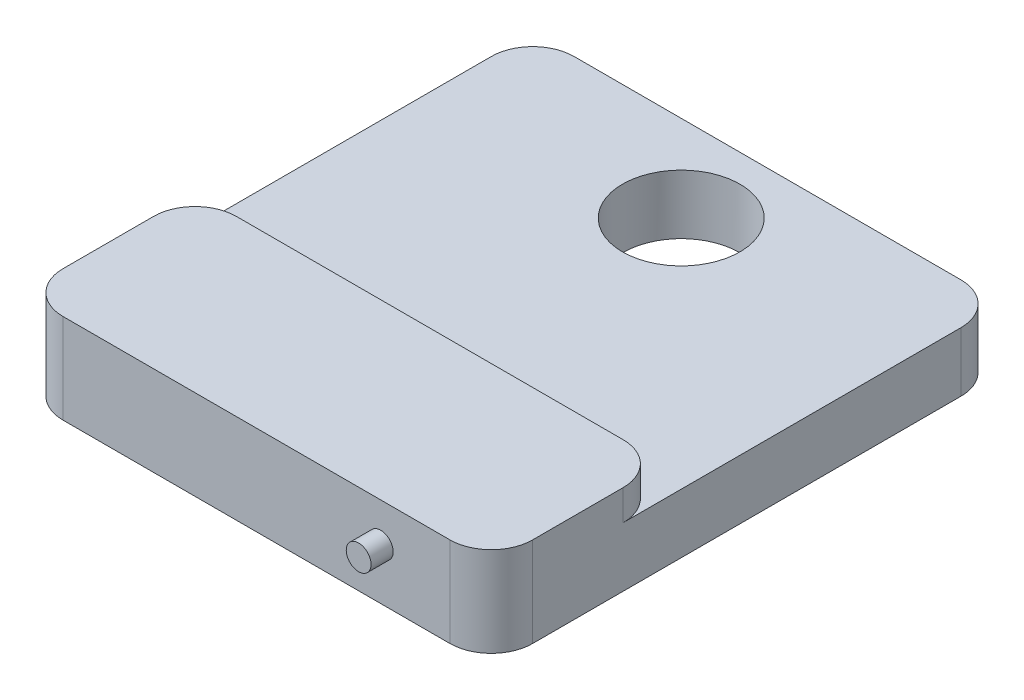
SolidWorks part; units mm, degrees
material "ABS"
ref_plane "Front Plane" through (0, 0, 0) normal (0, 0, 1) x (1, 0, 0)
ref_plane "Top Plane" through (0, 0, 0) normal (0, 1, 0) x (1, 0, 0)
ref_plane "Right Plane" through (0, 0, 0) normal (1, 0, 0) x (0, 0, -1)
sketch "Sketch1" plane through (0, 0, 0) normal (0, 1, 0) x (1, 0, 0)
  line L1 (0, 0) -> (215.9, 0)
  line L2 (0, 0) -> (0, 234.95)
  line L3 (0, 234.95) -> (215.9, 234.95)
  line L4 (215.9, 0) -> (215.9, 234.95)
  dimension "D1" = 234.95
  dimension "D2" = 215.9
extrude "Boss-Extrude1" add sketch "Sketch1" along normal blind 41.275
fillet "Fillet1" radius 19.05 4 edges at (0, 20.6375, -234.95) (215.9, 20.6375, -234.95) (215.9, 20.6375, 0) (0, 20.6375, 0)
sketch "Sketch3" plane through (0, 41.275, 0) normal (0, 1, 0) x (1, 0, 0)
  line L0 (107.95, 234.95) -> (107.95, 0) construction
  line L1 (196.85, 234.95) -> (19.05, 234.95) construction
  line L2 (19.05, 0) -> (196.85, 0) construction
  circle A0 centre (107.95, 195.2625) radius 26.9875
  point P8 (107.95, 222.25)
  dimension "D1" = 53.975
  dimension "D2" = 12.7
extrude "Cut-Extrude1" cut sketch "Sketch3" against normal up to next
sketch "Sketch4" plane through (0, 41.275, 0) normal (0, 1, 0) x (1, 0, 0)
  line L0 (215.9, 79.6925) -> (0, 79.6925)
  line L1 (215.9, 19.05) -> (215.9, 215.9) construction
  line L3 (196.85, 234.95) -> (19.05, 234.95) construction
  line L4 (0, 215.9) -> (0, 19.05) construction
  line L6 (196.85, 234.95) -> (19.05, 234.95)
  line L7 (215.9, 79.6925) -> (215.9, 215.9)
  line L8 (0, 215.9) -> (0, 79.6925)
  line L9 (19.05, 0) -> (196.85, 0) construction
  arc A0 (19.05, 234.95) -> (0, 215.9) centre (19.05, 215.9) ccw construction
  arc A1 (215.9, 215.9) -> (196.85, 234.95) centre (196.85, 215.9) ccw construction
  arc A4 (19.05, 234.95) -> (0, 215.9) centre (19.05, 215.9) ccw
  arc A5 (215.9, 215.9) -> (196.85, 234.95) centre (196.85, 215.9) ccw
  dimension "D1" = 79.6925
extrude "Cut-Extrude2" cut sketch "Sketch4" against normal blind 13.97
fillet "Fillet2" radius 19.05 2 edges at (0, 34.29, -79.6925) (215.9, 34.29, -79.6925)
sketch "Sketch5" plane through (0, 0, 0) normal (0, 0, 1) x (1, 0, 0)
  line L0 (215.9, 41.275) -> (215.9, 0) construction
  line L1 (19.05, 41.275) -> (196.85, 41.275) construction
  circle A0 centre (165.1, 23.495) radius 5.715
  dimension "D1" = 11.43
  dimension "D2" = 50.8
  dimension "D3" = 17.78
extrude "Boss-Extrude2" add sketch "Sketch5" along normal blind 10.16
